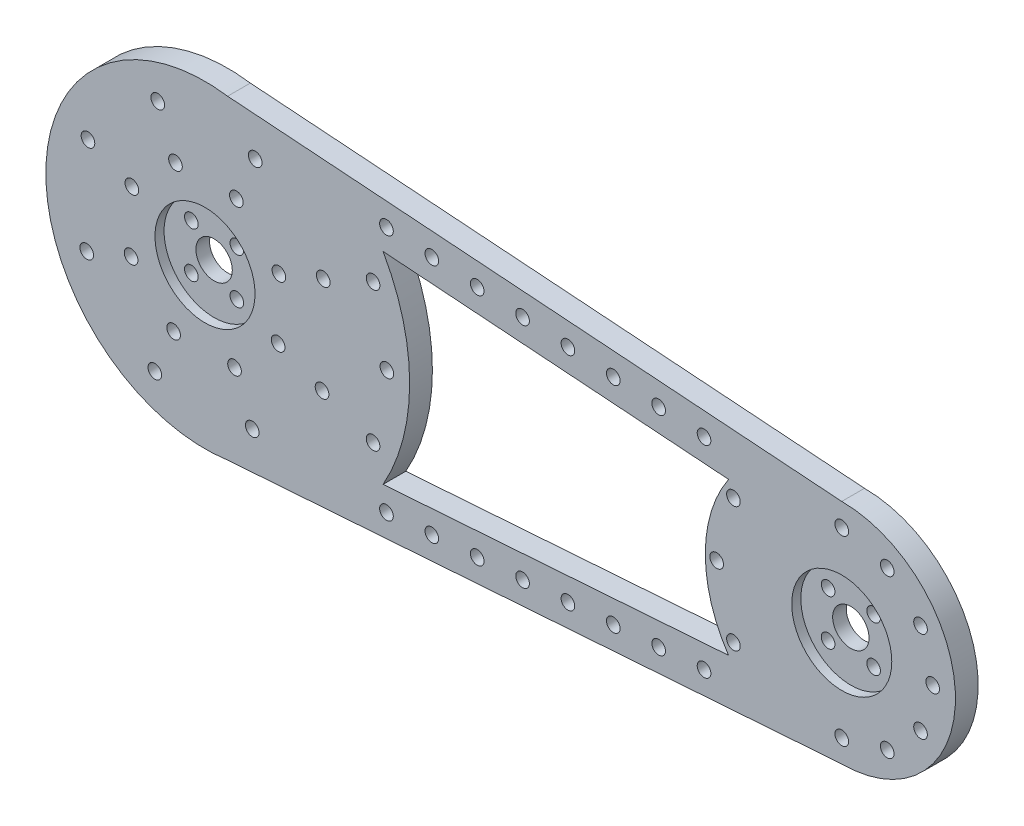
SolidWorks part; units mm, degrees
ref_plane "前视基准面" through (0, 0, 0) normal (0, 0, 1) x (1, 0, 0)
ref_plane "上视基准面" through (0, 0, 0) normal (0, 1, 0) x (1, 0, 0)
ref_plane "右视基准面" through (0, 0, 0) normal (1, 0, 0) x (0, 0, -1)
other "Configuration Table"
sketch "草图1" plane through (0, 0, 0) normal (0, 0, 1) x (1, 0, 0)
  line L0 (0, 0) -> (140, 0)
  line L1 (0, 35) -> (140, 25)
  line L2 (0, -35) -> (140, -25)
  circle A0 centre (0, 0) radius 35
  circle A1 centre (140, 0) radius 25
  dimension "D1" = 70
  dimension "D3" = 50
  dimension "D2" = 140
extrude "凸台-拉伸3" add sketch "草图1" along normal blind 5 contours A0 L1 L2 | A1 L0 A0 L2 | A1 L1 A0 L0 | A1 region at (72.7482, 16.0498, 0) region at (-0.0004, 0, 0) region at (72.7482, -16.0498, 0) region at (122.8223, 17.1777, 0)
sketch "草图4" plane through (0, 0, 5) normal (0, 0, 1) x (1, 0, 0)
  line L1 (-5, -5) -> (5, -5)
  line L2 (-5, -5) -> (-5, 5)
  line L3 (-5, 5) -> (5, 5)
  line L4 (5, -5) -> (5, 5)
  line L5 (-5, -5) -> (5, 5) construction
  line L6 (-5, 5) -> (5, -5) construction
  line L7 (135, -5) -> (145, -5)
  line L8 (135, -5) -> (135, 5)
  line L9 (135, 5) -> (145, 5)
  line L10 (145, -5) -> (145, 5)
  line L11 (135, -5) -> (145, 5) construction
  line L12 (135, 5) -> (145, -5) construction
  circle A0 centre (0, 0) radius 4
  circle A1 centre (-5, 5) radius 1.5
  circle A2 centre (5, 5) radius 1.5
  circle A3 centre (5, -5) radius 1.5
  circle A4 centre (-5, -5) radius 1.5
  circle A5 centre (140, 0) radius 4
  circle A6 centre (135, 5) radius 1.5
  circle A7 centre (145, 5) radius 1.5
  circle A8 centre (145, -5) radius 1.5
  circle A9 centre (135, -5) radius 1.5
  dimension "D1" = 8
  dimension "D4" = 3
  dimension "D6" = 8
  dimension "D9" = 3
  dimension "D2" = 10
  dimension "D3" = 10
  dimension "D7" = 10
  dimension "D8" = 10
  dimension "D5" = 4
  dimension "D10" = 4
extrude "切除-拉伸3" cut sketch "草图4" against normal blind 5 contours A5 | A0 | L2 A4 L1 | L1 A4 L2 | A6 | A9 | A8 | A7 | A1 | A2 | A3 region at (-4.3634, -4.3634, 5) region at (-5.2122, -5.2122, 5) region at (0, 0, 5) region at (140, 0, 5)
sketch "草图5" plane through (0, 0, 5) normal (0, 0, 1) x (1, 0, 0)
  circle A0 centre (0, 0) radius 11
  circle A1 centre (140, 0) radius 11
  dimension "D1" = 22
  dimension "D2" = 22
extrude "切除-拉伸4" cut sketch "草图5" against normal blind 2
sketch "草图6" plane through (0, 0, 5) normal (0, 0, 1) x (1, 0, 0)
  circle A0 centre (0, 0) radius 30
  circle A1 centre (0, 30) radius 1.5
  circle A2 centre (15, 25.9808) radius 1.5
  circle A3 centre (25.9808, 15) radius 1.5
  circle A4 centre (30, 0) radius 1.5
  circle A5 centre (25.9808, -15) radius 1.5
  circle A6 centre (15, -25.9808) radius 1.5
  circle A7 centre (0, -30) radius 1.5
  circle A8 centre (-15, -25.9808) radius 1.5
  circle A9 centre (-25.9808, -15) radius 1.5
  circle A10 centre (-30, 0) radius 1.5
  circle A11 centre (-25.9808, 15) radius 1.5
  circle A12 centre (-15, 25.9808) radius 1.5
  circle A13 centre (140, 0) radius 20
  circle A14 centre (140, 20) radius 1.5
  circle A15 centre (150, 17.3205) radius 1.5
  circle A16 centre (157.3205, 10) radius 1.5
  circle A17 centre (160, 0) radius 1.5
  circle A18 centre (157.3205, -10) radius 1.5
  circle A19 centre (150, -17.3205) radius 1.5
  circle A20 centre (140, -20) radius 1.5
  circle A21 centre (130, -17.3205) radius 1.5
  circle A22 centre (122.6795, -10) radius 1.5
  circle A23 centre (120, 0) radius 1.5
  circle A24 centre (122.6795, 10) radius 1.5
  circle A25 centre (130, 17.3205) radius 1.5
  point P29 (0, 0)
  dimension "D1" = 60
  dimension "D2" = 3
  dimension "D4" = 40
  dimension "D5" = 3
  dimension "D3" = 12
  dimension "D6" = 12
extrude "切除-拉伸6" cut sketch "草图6" against normal through all contours A0 A12 | A11 | A12 | A1 | A2 | A3 | A4 | A5 | A6 | A7 | A8 | A9 | A10 | A25 | A14 | A15 | A16 | A17 | A18 | A19 | A20 | A21 | A22 | A23 | A24 region at (-14.6783, 25.4236, 5)
sketch "草图8" plane through (0, 0, 5) normal (0, 0, 1) x (1, 0, 0)
  line L4 (-0.1715, -29.9995) -> (139.8316, -19.9993)
  line L5 (139.8316, 19.9993) -> (-0.1715, 29.9995)
  line L6 (-0.1715, -29.9995) -> (139.8316, -19.9993)
  line L7 (139.8316, 19.9993) -> (-0.1715, 29.9995)
  line L8 (-0.7125, 25.0254) -> (139.2875, 15.0254)
  line L9 (-0.7125, 25.0254) -> (139.2875, 15.0254)
  line L11 (-0.7125, -25.0254) -> (139.2875, -15.0254)
  line L12 (-0.7125, -25.0254) -> (139.2875, -15.0254)
  circle A3 centre (0, 30) radius 1.5
  arc A4 (139.8316, -19.9993) -> (139.8316, 19.9993) centre (140, 0) ccw
  arc A5 (-0.1715, 29.9995) -> (-0.1715, -29.9995) centre (0, 0) ccw
  arc A6 (139.8316, -19.9993) -> (139.8316, 19.9993) centre (140, 0) ccw
  arc A7 (-0.1715, 29.9995) -> (-0.1715, -29.9995) centre (0, 0) ccw
  circle A8 centre (9.9746, 29.2875) radius 1.5
  circle A9 centre (19.9492, 28.5751) radius 1.5
  circle A10 centre (29.9238, 27.8626) radius 1.5
  circle A11 centre (39.8983, 27.1501) radius 1.5
  circle A12 centre (49.8729, 26.4376) radius 1.5
  circle A13 centre (59.8475, 25.7252) radius 1.5
  circle A14 centre (69.8221, 25.0127) radius 1.5
  circle A15 centre (79.7967, 24.3002) radius 1.5
  circle A16 centre (89.7713, 23.5878) radius 1.5
  circle A17 centre (99.7459, 22.8753) radius 1.5
  circle A18 centre (109.7205, 22.1628) radius 1.5
  circle A19 centre (119.695, 21.4504) radius 1.5
  circle A20 centre (129.6696, 20.7379) radius 1.5
  circle A21 centre (0, -30) radius 1.5
  circle A22 centre (9.9746, -29.2875) radius 1.5
  circle A23 centre (19.9492, -28.5751) radius 1.5
  circle A24 centre (29.9238, -27.8626) radius 1.5
  circle A25 centre (39.8983, -27.1501) radius 1.5
  circle A26 centre (49.8729, -26.4376) radius 1.5
  circle A27 centre (59.8475, -25.7252) radius 1.5
  circle A28 centre (69.8221, -25.0127) radius 1.5
  circle A29 centre (79.7967, -24.3002) radius 1.5
  circle A30 centre (89.7713, -23.5878) radius 1.5
  circle A31 centre (99.7459, -22.8753) radius 1.5
  circle A32 centre (109.7205, -22.1628) radius 1.5
  circle A33 centre (119.695, -21.4504) radius 1.5
  circle A34 centre (129.6696, -20.7379) radius 1.5
  circle A35 centre (0, 0) radius 35
  circle A36 centre (140, 0) radius 25
  dimension "D2" = 14
  dimension "D1" = 5
  dimension "D4" = 10
  dimension "D5" = 10
  dimension "D3" = 14
extrude "切除-拉伸8" cut sketch "草图8" against normal through all contours A36 L9 A35 L12 | L6 A25 | L6 A25 | A8 | A9 | A10 | A11 | A12 | A13 | A14 | A16 | A15 | A17 | A18 | A19 | A20 | A34 | A33 | A32 | A31 | A30 | A29 | A28 | A27 | A26 | A24 | A23 | A22 region at (72.4357, 0, 5) region at (39.8525, -26.5083, 5) region at (39.9432, -27.7783, 5)
sketch "草图9" plane through (0, 0, 5) normal (0, 0, 1) x (1, 0, 0)
  circle A0 centre (15, 25.9808) radius 1.5
  circle A1 centre (15, -25.9808) radius 1.5
extrude "凸台-拉伸4" add sketch "草图9" against normal blind 5
sketch "草图10" plane through (0, 0, 5) normal (0, 0, 1) x (1, 0, 0)
  circle A0 centre (130, -17.3205) radius 1.5
  circle A1 centre (130, 17.3205) radius 1.5
extrude "凸台-拉伸6" add sketch "草图10" against normal blind 5
sketch "草图11" plane through (0, 0, 5) normal (0, 0, 1) x (1, 0, 0)
  circle A0 centre (25.9808, -15) radius 1.5
  circle A1 centre (30, 0) radius 1.5
  circle A2 centre (25.9808, 15) radius 1.5
  circle A3 centre (122.6795, -10) radius 1.5
  circle A4 centre (120, 0) radius 1.5
  circle A5 centre (122.6795, 10) radius 1.5
  circle A6 centre (119.695, 21.4504) radius 1.5
  circle A7 centre (119.695, -21.4504) radius 1.5
  circle A8 centre (29.9238, -27.8626) radius 1.5
  circle A9 centre (29.9238, 27.8626) radius 1.5
  circle A10 centre (0, 0) radius 11
  circle A11 centre (0, 0) radius 35
  circle A12 centre (19.9492, -28.5751) radius 1.5
  circle A13 centre (19.9492, 28.5751) radius 1.5
  circle A14 centre (140, 0) radius 11
  circle A15 centre (140, 0) radius 24.9365
  circle A16 centre (129.6696, -20.7379) radius 1.5
  circle A17 centre (129.6696, 20.7379) radius 1.5
extrude "凸台-拉伸12" add sketch "草图11" against normal blind 5 contours A16 | A7 | A6 | A13 A11 A12 A0 A1 A2 A10 | A1 | A2 | A11 A13 | A11 A13 | A9 | A8 | A17 | A12 | A0 region at (30, 0, 5) region at (25.9808, 15, 5) region at (119.695, 21.4504, 5) region at (119.695, -21.4504, 5) region at (29.9238, -27.8626, 5) region at (29.9238, 27.8626, 5) region at (30.4854, -15.0772, 5) region at (19.6276, 28.1144, 5) region at (20.3571, 29.1594, 5) region at (129.6696, -20.7379, 5)
sketch "草图14" plane through (0, 0, 0) normal (0, 0, -1) x (-1, 0, 0)
  circle A2 centre (-11.0396, 25.7318) radius 1.5
  circle A3 centre (-6.8997, 16.0824) radius 1.5
  circle A4 centre (6.4931, 16.2508) radius 1.5
  circle A5 centre (10.389, 26.0013) radius 1.5
  circle A6 centre (16.0824, 6.8997) radius 1.5
  circle A7 centre (25.7318, 11.0396) radius 1.5
  circle A8 centre (16.2508, -6.4931) radius 1.5
  circle A9 centre (26.0013, -10.389) radius 1.5
  circle A10 centre (6.8997, -16.0824) radius 1.5
  circle A11 centre (11.0396, -25.7318) radius 1.5
  circle A12 centre (-6.4931, -16.2508) radius 1.5
  circle A13 centre (-10.389, -26.0013) radius 1.5
  circle A14 centre (-16.0824, -6.8997) radius 1.5
  circle A15 centre (-25.7318, -11.0396) radius 1.5
  circle A16 centre (-16.2508, 6.4931) radius 1.5
  circle A17 centre (-26.0013, 10.389) radius 1.5
  point P41 (0, 0)
  dimension "D1" = 8
extrude "切除-拉伸9" cut sketch "草图14" against normal blind 5
sketch "草图15" plane through (0, 0, 0) normal (0, 0, -1) x (-1, 0, 0)
  line L0 (-26.2977, -23.0961) -> (-32.9913, -22.618)
  line L1 (-26.2977, -23.0961) -> (-121.0676, -16.3268) construction
  line L2 (-26.2977, 23.0961) -> (-32.9913, 22.618)
  line L3 (-26.2977, 23.0961) -> (-121.0676, 16.3268) construction
  circle A0 centre (0, 0) radius 35
  circle A1 centre (0, 0) radius 40
  dimension "D1" = 80
extrude "凸台-拉伸13" add sketch "草图15" against normal blind 5 contours L2 A1 L0 A0 region at (29.6102, -22.3765, 0)
sketch "草图16" plane through (0, 0, 0) normal (0, 0, -1) x (-1, 0, 0)
  circle A1 centre (-35, 0) radius 1.5
  circle A2 centre (-32.3358, 13.3939) radius 1.5
  circle A16 centre (-32.3358, -13.3939) radius 1.5
  circle A17 centre (-24.7487, 24.7487) radius 1.5 [skipped]
  circle A18 centre (-24.7487, -24.7487) radius 1.5 [skipped]
  circle A19 centre (-13.3939, -32.3358) radius 1.5 [skipped]
  circle A20 centre (-13.3939, 32.3358) radius 1.5 [skipped]
  circle A21 centre (0, 35) radius 1.5 [skipped]
  circle A22 centre (13.3939, 32.3358) radius 1.5 [skipped]
  circle A23 centre (24.7487, 24.7487) radius 1.5 [skipped]
  circle A24 centre (32.3358, 13.3939) radius 1.5 [skipped]
  circle A25 centre (35, 0) radius 1.5 [skipped]
  circle A26 centre (32.3358, -13.3939) radius 1.5 [skipped]
  circle A27 centre (24.7487, -24.7487) radius 1.5 [skipped]
  circle A28 centre (13.3939, -32.3358) radius 1.5 [skipped]
  circle A29 centre (0, -35) radius 1.5 [skipped]
  dimension "D1" = 3
  dimension "D2" = 16
extrude "切除-拉伸10" cut sketch "草图16" against normal blind 5
sketch "草图18" plane through (0, 0, 5) normal (0, 0, 1) x (1, 0, 0)
  line L0 (32.9913, 22.618) -> (39.1555, 22.1777)
  line L1 (32.9913, 22.618) -> (121.0676, 16.3268) construction
  line L2 (32.9913, -22.618) -> (39.1555, -22.1777)
  line L3 (32.9913, -22.618) -> (121.0676, -16.3268) construction
  circle A0 centre (0, 0) radius 40
  circle A1 centre (0, 0) radius 45
  dimension "D1" = 90
extrude "凸台-拉伸14" add sketch "草图18" against normal blind 5 contours L2 A1 L0 A0 region at (40.3299, 0, 5)
sketch "草图19" plane through (0, 0, 5) normal (0, 0, 1) x (1, 0, 0)
  circle A0 centre (32.3358, 13.3939) radius 1.5
  circle A1 centre (35, 0) radius 1.5
  circle A2 centre (32.3358, -13.3939) radius 1.5
extrude "凸台-拉伸15" add sketch "草图19" against normal blind 5
sketch "草图20" plane through (0, 0, 0) normal (0, 0, -1) x (-1, 0, 0)
  circle A1 centre (-40, 0) radius 1.5
  circle A2 centre (-36.9552, 15.3073) radius 1.5
  circle A4 centre (-15.3073, 36.9552) radius 1.5
  circle A5 centre (0, 40) radius 1.5
  circle A6 centre (15.3073, 36.9552) radius 1.5
  circle A7 centre (28.2843, 28.2843) radius 1.5
  circle A8 centre (36.9552, 15.3073) radius 1.5
  circle A9 centre (40, 0) radius 1.5
  circle A10 centre (36.9552, -15.3073) radius 1.5
  circle A11 centre (28.2843, -28.2843) radius 1.5
  circle A12 centre (15.3073, -36.9552) radius 1.5
  circle A13 centre (0, -40) radius 1.5
  circle A14 centre (-15.3073, -36.9552) radius 1.5
  circle A16 centre (-36.9552, -15.3073) radius 1.5
  circle A17 centre (-28.2843, -28.2843) radius 1.5 [skipped]
  circle A18 centre (-28.2843, 28.2843) radius 1.5 [skipped]
  point P38 (0, 0)
  dimension "D2" = 3
  dimension "D3" = 16
extrude "切除-拉伸11" cut sketch "草图20" against normal blind 5
sketch "草图21" plane through (0, 0, 0) normal (0, 0, -1) x (-1, 0, 0)
  line L0 (-121.0676, 16.3268) -> (-115.113, 16.7522)
  line L1 (-39.1555, 22.1777) -> (-121.0676, 16.3268) construction
  line L2 (-121.0676, -16.3268) -> (-115.113, -16.7522)
  line L3 (-39.1555, -22.1777) -> (-121.0676, -16.3268) construction
  circle A0 centre (-140, 0) radius 25
  circle A1 centre (-140, 0) radius 27.5
  circle A2 centre (-140, 0) radius 30
  point P15 (-115.113, 16.7522)
  point P16 (-121.0676, -16.3268)
  dimension "D1" = 50
  dimension "D2" = 55
  dimension "D3" = 60
extrude "凸台-拉伸16" add sketch "草图21" against normal blind 5 contours L2 A1 L0 A0 | L2 A2 L0 A1 region at (119.5259, 16.0943, 0) region at (116.5483, 16.3042, 0)
sketch "草图22" plane through (0, 0, 5) normal (0, 0, 1) x (1, 0, 0)
  circle A1 centre (122.6795, 10) radius 1.5
  circle A2 centre (120, 0) radius 1.5
  circle A3 centre (122.6795, -10) radius 1.5
extrude "凸台-拉伸17" add sketch "草图22" against normal blind 5
sketch "草图23" plane through (0, 0, 5) normal (0, 0, 1) x (1, 0, 0)
  circle A0 centre (140, 0) radius 27.5
  circle A1 centre (112.5, 0) radius 1.5
  circle A2 centre (116.1843, 13.75) radius 1.5
  circle A4 centre (140, 27.5) radius 1.5
  circle A5 centre (153.75, 23.8157) radius 1.5
  circle A6 centre (163.8157, 13.75) radius 1.5
  circle A7 centre (167.5, 0) radius 1.5
  circle A8 centre (163.8157, -13.75) radius 1.5
  circle A9 centre (153.75, -23.8157) radius 1.5
  circle A10 centre (140, -27.5) radius 1.5
  circle A12 centre (116.1843, -13.75) radius 1.5
  circle A13 centre (126.25, 23.8157) radius 1.5 [skipped]
  circle A14 centre (126.25, -23.8157) radius 1.5 [skipped]
  dimension "D1" = 55
  dimension "D2" = 3
  dimension "D3" = 12
extrude "切除-拉伸15" cut sketch "草图23" against normal blind 5 contours A0 A2 | A0 A12 | A0 A12 | A1 | A2 region at (115.6394, 14.0646, 5) region at (115.6394, -14.0646, 5) region at (116.742, -13.428, 5)
